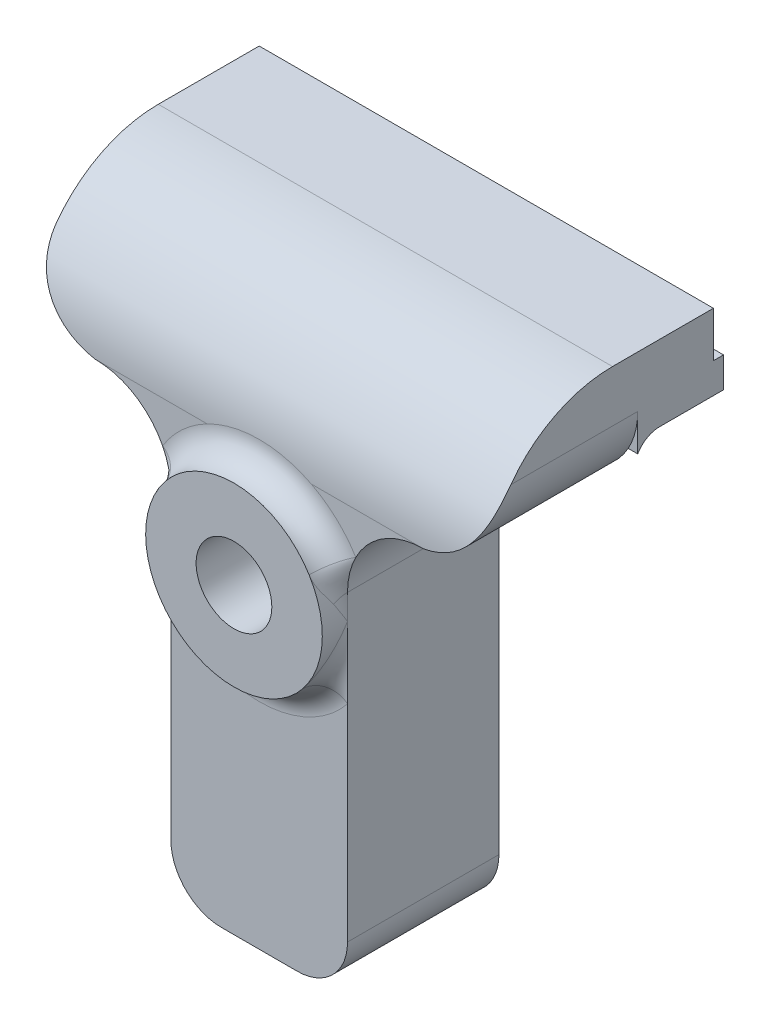
SolidWorks part; units mm, degrees
ref_plane "Ön Düzlem" through (0, 0, 0) normal (0, 0, 1) x (1, 0, 0)
ref_plane "Üst Düzlem" through (0, 0, 0) normal (0, 1, 0) x (1, 0, 0)
ref_plane "Sağ Düzlem" through (0, 0, 0) normal (1, 0, 0) x (0, 0, -1)
sketch "Çizim2" plane through (0, 0, 0) normal (0, 0, 1) x (1, 0, 0)
  line L0 (-17.5, 0) -> (17.5, 0)
  line L1 (17.5, 0) -> (17.5, 70)
  line L2 (45, 110) -> (-45, 110)
  line L3 (0, 123.1633) -> (0, -11.7574) construction
  line L4 (45, 110) -> (45, 99.7902)
  line L5 (0, 150.4444) -> (0, -40.0534) construction
  line L6 (-45, 110) -> (-45, 99.7902)
  line L7 (-17.5, 0) -> (-17.5, 70)
  arc A0 (45, 99.7902) -> (32.5, 85) centre (30, 99.7902) cw
  arc A1 (32.5, 85) -> (17.5, 70) centre (32.5, 70) ccw
  arc A2 (-32.5, 85) -> (-17.5, 70) centre (-32.5, 70) cw
  arc A3 (-45, 99.7902) -> (-32.5, 85) centre (-30, 99.7902) ccw
  point P4 (0, 0)
  point P21 (0, 110)
  point P22 (0, 0)
  dimension "D3" = 15
  dimension "D1" = 15
  dimension "D2" = 17.5
  dimension "D4" = 85
  dimension "D5" = 110
  dimension "D6" = 45
extrude "Yükseklik-Ekstrüzyon1" add sketch "Çizim2" along normal blind 30
sketch "Çizim3" plane through (0, 0, 30) normal (0, 0, 1) x (1, 0, 0)
  line L0 (-17.5, 0) -> (17.5, 0) construction
  line L1 (-7.5, 10) -> (7.5, 10) construction
  line L2 (-9.5, 12) -> (-9.5, 42) construction
  line L3 (-7.5, 44) -> (7.5, 44) construction
  line L4 (9.5, 12) -> (9.5, 42) construction
  line L5 (-9.5, 10) -> (9.5, 44) construction
  line L6 (-9.5, 44) -> (9.5, 10) construction
  arc A0 (7.5, 10) -> (9.5, 12) centre (7.5, 12) ccw construction
  arc A1 (-9.5, 42) -> (-7.5, 44) centre (-7.5, 42) cw construction
  arc A2 (-7.5, 10) -> (-9.5, 12) centre (-7.5, 12) cw construction
  arc A3 (7.5, 44) -> (9.5, 42) centre (7.5, 42) cw construction
  circle A4 centre (0, 65) radius 7.5
  point P0 (0, 27)
  dimension "D1" = 2
  dimension "D6" = 15
  dimension "D2" = 30
  dimension "D3" = 10
  dimension "D4" = 15
  dimension "D5" = 0
extrude "Kes-Ekstrüzyon1" cut sketch "Çizim3" against normal blind 41
fillet "Radyus1" radius 10 2 edges at (-17.5, 0, 15) (17.5, 0, 15)
sketch "Çizim4" plane through (0, 0, 30) normal (0, 0, 1) x (1, 0, 0)
  circle A0 centre (0, 65) radius 17.5
  circle A1 centre (0, 65) radius 7.5 construction
  circle A2 centre (0, 65) radius 7.5
extrude "Yükseklik-Ekstrüzyon2" add sketch "Çizim4" along normal blind 5
fillet "Radyus2" radius 5 2 edges at (0, 82.5, 30) (0, 47.5, 30)
ref_plane "Düzlem1" through (50, 0, 0) normal (1, 0, 0) x (0, 0, -1)
sketch "Çizim8" plane through (50, 0, 0) normal (1, 0, 0) x (0, 0, -1)
  line L3 (-30, 85) -> (-30, 110)
  line L4 (-30, 110) -> (-5, 110)
  arc A0 (-5, 110) -> (-30, 85) centre (-5, 85) ccw
  dimension "D1" = 25
extrude "Kes-Ekstrüzyon2" cut sketch "Çizim8" against normal blind 147
sketch "Çizim9" plane through (0, 0, 0) normal (1, 0, 0) x (0, 0, -1)
  line L0 (0, 110) -> (15, 110)
  line L1 (15, 110) -> (15, 101)
  line L2 (15, 101) -> (17, 101)
  line L3 (17, 101) -> (17, 95)
  line L4 (17, 95) -> (4.332, 95)
  line L5 (0, 85) -> (0, 99.7902) construction
  line L6 (0, 92.4968) -> (0, 110)
  arc A0 (4.332, 95) -> (0, 92.4968) centre (4.332, 90) ccw
  point P12 (0, 97.4968)
  dimension "D1" = 5
  dimension "D2" = 15
  dimension "D3" = 0
  dimension "D4" = 2
  dimension "D5" = 9
  dimension "D6" = 15
extrude "Yükseklik-Ekstrüzyon3" add sketch "Çizim9" along normal mid plane 90
sketch "Çizim10" plane through (0, 0, -15) normal (0, 0, -1) x (-1, 0, 0)
  line L0 (0, 117.0325) -> (0, -22.4054) construction
  line L1 (-45, 101) -> (-45, 110) construction
  circle A0 centre (-25, 105.5) radius 3
  circle A1 centre (25, 105.5) radius 3
  dimension "D1" = 20
  dimension "D2" = 4.5
extrude "Kes-Ekstrüzyon3" cut sketch "Çizim10" against normal blind 20
sketch "Çizim11" plane through (0, 0, 0) normal (0, 0, -1) x (-1, 0, 0)
  line L0 (17.5, 70) -> (17.5, 10) construction
  line L1 (-5.5, 10) -> (5.5, 10)
  line L2 (-7.5, 12) -> (-7.5, 38)
  line L3 (-5.5, 40) -> (5.5, 40)
  line L4 (7.5, 12) -> (7.5, 38)
  line L5 (-7.5, 10) -> (7.5, 40) construction
  line L6 (-7.5, 40) -> (7.5, 10) construction
  line L7 (-17.5, 10) -> (-17.5, 70) construction
  arc A2 (-7.5, 38) -> (-5.5, 40) centre (-5.5, 38) cw
  arc A3 (5.5, 10) -> (7.5, 12) centre (5.5, 12) ccw
  arc A4 (-5.5, 10) -> (-7.5, 12) centre (-5.5, 12) cw
  arc A5 (5.5, 40) -> (7.5, 38) centre (5.5, 38) cw
  point P0 (0, 25)
  dimension "D5" = 2
  dimension "D1" = 10
  dimension "D2" = 10
  dimension "D3" = 30
extrude "Kes-Ekstrüzyon4" cut sketch "Çizim11" against normal blind 25
